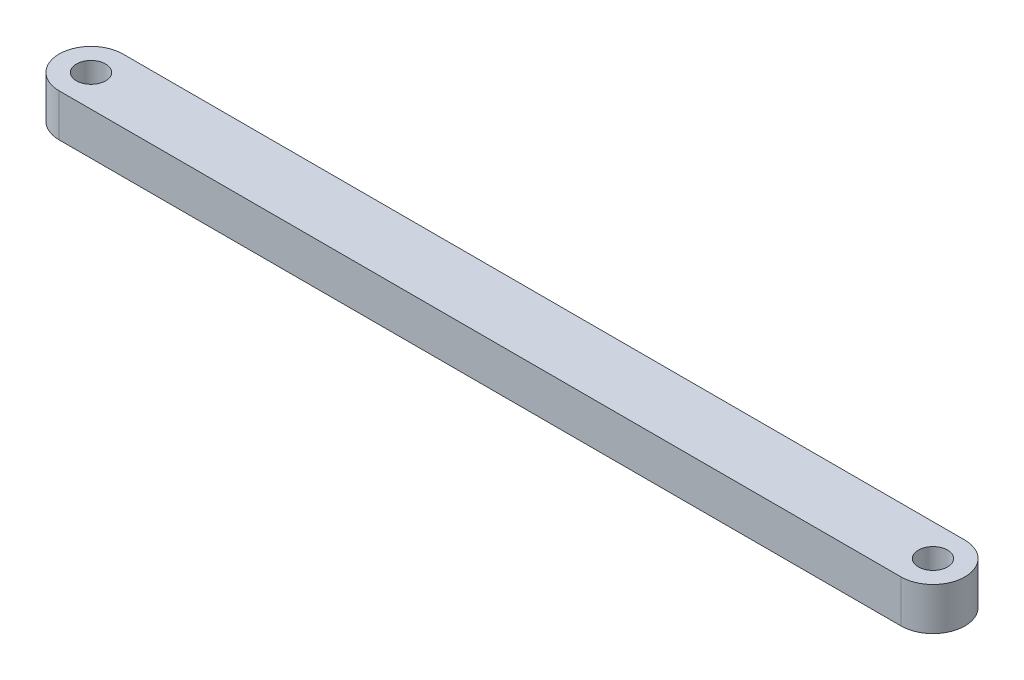
SolidWorks part; units mm, degrees
ref_plane "Front Plane" through (0, 0, 0) normal (0, 0, 1) x (1, 0, 0)
ref_plane "Top Plane" through (0, 0, 0) normal (0, 1, 0) x (1, 0, 0)
ref_plane "Right Plane" through (0, 0, 0) normal (1, 0, 0) x (0, 0, -1)
sketch "Sketch1" plane through (0, 0, 0) normal (0, 1, 0) x (1, 0, 0)
  line L0 (0, 0) -> (125.7224, 0) construction
  line L1 (0, 4.7625) -> (125.7224, 4.7625)
  line L2 (0, -4.7625) -> (125.7224, -4.7625)
  arc A0 (0, 4.7625) -> (0, -4.7625) centre (0, 0) ccw
  arc A1 (125.7224, -4.7625) -> (125.7224, 4.7625) centre (125.7224, 0) ccw
  circle A2 centre (0, 0) radius 2.1828
  circle A3 centre (125.7224, 0) radius 2.1828
  point P3 (62.8612, 0)
  dimension "D2" = 4.7625
  dimension "D3" = 4.3656
  dimension "D4" = 4.3656
  dimension "D1" = 125.7224
extrude "Boss-Extrude1" add sketch "Sketch1" along normal blind 6.35
